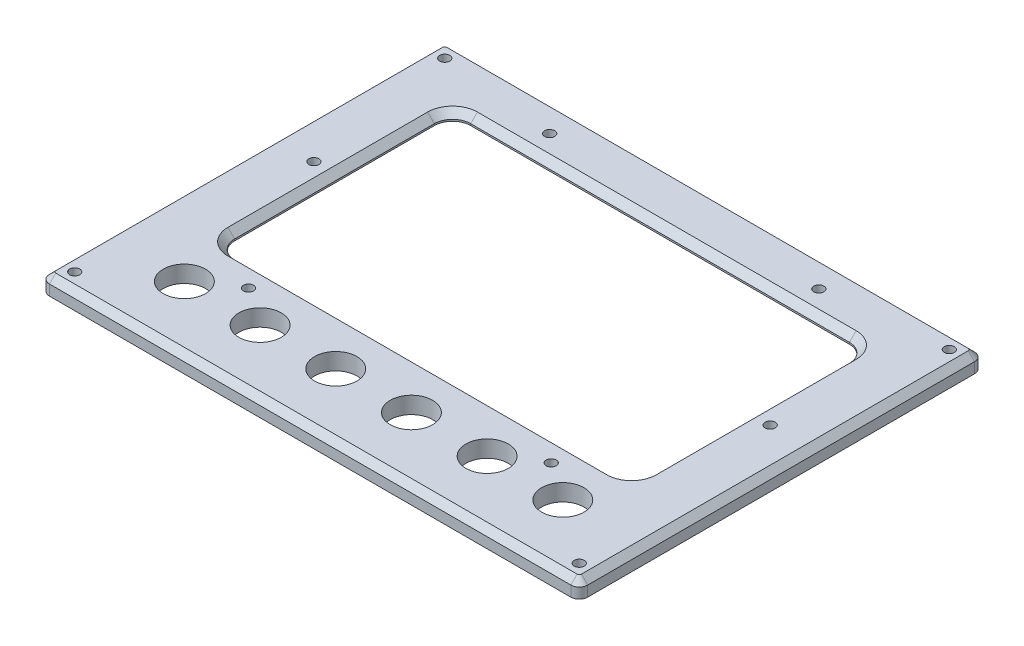
SolidWorks part; units mm, degrees
material "6061-T6 (SS)"
ref_plane "Front Plane" through (0, 0, 0) normal (0, 0, 1) x (1, 0, 0)
ref_plane "Top Plane" through (0, 0, 0) normal (0, 1, 0) x (1, 0, 0)
ref_plane "Right Plane" through (0, 0, 0) normal (1, 0, 0) x (0, 0, -1)
sketch "Sketch1" plane through (0, 0, 0) normal (0, 1, 0) x (1, 0, 0)
  line L1 (-101.6, 64.8558) -> (101.6, 64.8558)
  line L2 (-101.6, 64.8558) -> (-101.6, -87.5442)
  line L3 (-101.6, -87.5442) -> (101.6, -87.5442)
  line L4 (101.6, 64.8558) -> (101.6, -87.5442)
  line L5 (-101.6, 64.8558) -> (101.6, -87.5442) construction
  line L6 (-101.6, -87.5442) -> (101.6, 64.8558) construction
  point P0 (0, -11.3442)
  dimension "D1" = 203.2
  dimension "D2" = 152.4
extrude "Boss-Extrude1" add sketch "Sketch1" along normal blind 6.35
sketch "Sketch2" plane through (0, 6.35, 0) normal (0, 1, 0) x (1, 0, 0)
  line L1 (-78.35, 44.55) -> (78.35, 44.55)
  line L2 (-78.35, 44.55) -> (-78.35, -44.55)
  line L3 (-78.35, -44.55) -> (78.35, -44.55)
  line L4 (78.35, 44.55) -> (78.35, -44.55)
  line L5 (-78.35, 44.55) -> (78.35, -44.55) construction
  line L6 (-78.35, -44.55) -> (78.35, 44.55) construction
  point P0 (0, 0)
  dimension "D1" = 156.7
  dimension "D2" = 89.1
extrude "Cut-Extrude1" cut sketch "Sketch2" against normal through all
fillet "Fillet2" radius 6.858 4 edges at (-78.35, 3.175, 44.55) (78.35, 3.175, 44.55) (78.35, 3.175, -44.55) (-78.35, 3.175, -44.55)
chamfer "Chamfer1" distance 2.54 angle 45 8 edges at (78.35, 6.35, 0) (0, 6.35, 44.55) (-78.35, 6.35, 0) (0, 6.35, -44.55) (76.3413, 6.35, 42.5413) (-76.3413, 6.35, 42.5413) (76.3413, 6.35, -42.5413) (-76.3413, 6.35, -42.5413)
sketch "Sketch7" plane through (0, 0, 0) normal (0, -1, 0) x (1, 0, 0)
  line L1 (-31.75, 54.075) -> (31.75, 54.075)
  line L2 (-31.75, 54.075) -> (-31.75, 44.55)
  line L3 (-31.75, 44.55) -> (31.75, 44.55)
  line L4 (31.75, 54.075) -> (31.75, 44.55)
  line L5 (-31.75, 54.075) -> (31.75, 44.55) construction
  line L6 (-31.75, 44.55) -> (31.75, 54.075) construction
  line L7 (-71.492, 44.55) -> (71.492, 44.55) construction
  point P0 (0, 49.3125)
  dimension "D1" = 63.5
  dimension "D2" = 9.525
extrude "Cut-Extrude4" cut sketch "Sketch7" against normal blind 3.175
fillet "Fillet1" radius 6.858 2 edges at (31.75, 1.5875, 54.075) (-31.75, 1.5875, 54.075)
sketch "Sketch4" plane through (0, 6.35, 0) normal (0, 1, 0) x (1, 0, 0)
  line L0 (-71.4375, -63.6) -> (-42.8625, -63.6) construction
  line L1 (-42.8625, -63.6) -> (-14.2875, -63.6) construction
  line L2 (-14.2875, -63.6) -> (14.2875, -63.6) construction
  line L3 (14.2875, -63.6) -> (42.8625, -63.6) construction
  line L5 (42.8625, -63.6) -> (71.4375, -63.6) construction
  line L6 (-14.2875, -63.6) -> (0, 0) construction
  line L7 (0, 0) -> (14.2875, -63.6) construction
  line L9 (-78.35, -44.55) -> (-31.2102, -44.55) construction
  circle A0 centre (-71.4375, -63.6) radius 8.001
  circle A1 centre (-42.8625, -63.6) radius 8.001
  circle A2 centre (-14.2875, -63.6) radius 8.001
  circle A3 centre (14.2875, -63.6) radius 8.001
  circle A4 centre (42.8625, -63.6) radius 8.001
  circle A5 centre (71.4375, -63.6) radius 8.001
  dimension "D1" = 16.002
  dimension "D2" = 28.575
  dimension "D3" = 19.05
extrude "Cut-Extrude3" cut sketch "Sketch4" against normal through all
fillet "Fillet3" radius 3.175 4 edges at (101.6, 3.175, 87.5442) (101.6, 3.175, -64.8558) (-101.6, 3.175, 87.5442) (-101.6, 3.175, -64.8558)
chamfer "Chamfer2" distance 2.3813 angle 45 8 edges at (101.6, 6.35, 11.3442) (0, 6.35, 87.5442) (0, 6.35, -64.8558) (-101.6, 6.35, 11.3442) (100.6701, 6.35, -63.9259) (100.6701, 6.35, 86.6143) (-100.6701, 6.35, -63.9259) (-100.6701, 6.35, 86.6143)
hole_wizard "#6 Clearance Hole1" positions "Sketch5" profile "Sketch6" hole size "#6" standard "ANSI Inch" end condition through all
sketch "Sketch5" plane through (0, 6.35, 0) normal (0, 1, 0) x (1, 0, 0)
  line L0 (-95.25, 58.5058) -> (0, 0) construction
  line L1 (0, 0) -> (95.25, 58.5058) construction
  line L3 (-98.425, 64.8558) -> (98.425, 64.8558) construction
  line L4 (98.425, -87.5442) -> (-98.425, -87.5442) construction
  line L5 (-101.6, -84.3692) -> (-101.6, 61.6808) construction
  point P0 (-95.25, 58.5058)
  point P2 (95.25, 58.5058)
  point P4 (95.25, -81.1942)
  point P6 (-95.25, -81.1942)
  dimension "D1" = 6.35
  dimension "D2" = 6.35
  dimension "D3" = 6.35
sketch "Sketch6" plane through (-95.25, 6.35, -58.5058) normal (1, 0, 0) x (0, 0, 1)
  line L0 (0, 0) -> (0, 6.35)
  line L1 (0, 6.35) -> (1.8986, 6.35)
  line L2 (1.8986, 6.35) -> (1.8986, 0)
  line L5 (1.8986, 0) -> (0, 0)
  line L11 (0, -6.35) -> (0, 107.95) construction
  dimension "Thru Hole Dia." = 3.7973
  dimension "Thru Hole Depth" = 6.35
sketch "Sketch8" plane through (0, 0, 0) normal (0, -1, 0) x (1, 0, 0)
  line L8 (-88.9, -52.1558) -> (88.9, -52.1558)
  line L9 (88.9, -52.1558) -> (88.9, 74.8442)
  line L10 (88.9, 74.8442) -> (-88.9, 74.8442)
  line L11 (-88.9, 74.8442) -> (-88.9, -52.1558)
  line L12 (-88.9, -52.1558) -> (88.9, -52.1558) construction
  line L13 (88.9, -52.1558) -> (88.9, 74.8442) construction
  line L14 (88.9, 74.8442) -> (-88.9, 74.8442) construction
  line L15 (-88.9, 74.8442) -> (-88.9, -52.1558) construction
  dimension "D1" = 12.7
extrude "Cut-Extrude5" cut sketch "Sketch9" against normal blind 3.175
sketch "Sketch9" plane through (0, 0, 0) normal (0, -1, 0) x (1, 0, 0)
  line L4 (82.45, -50) -> (-82.45, -50) construction
  line L5 (-82.45, -50) -> (-82.45, 50) construction
  line L6 (-82.45, 50) -> (82.45, 50) construction
  line L7 (82.45, 50) -> (82.45, -50) construction
  line L8 (-82.958, 50.508) -> (82.958, 50.508)
  line L9 (82.958, 50.508) -> (82.958, -50.508)
  line L10 (82.958, -50.508) -> (-82.958, -50.508)
  line L11 (-82.958, -50.508) -> (-82.958, 50.508)
sketch "Sketch10" plane through (0, 0, 0) normal (0, -1, 0) x (1, 0, 0)
  line L0 (-82.958, -50.508) -> (-82.958, -43.7728) construction
  line L1 (-82.958, -50.508) -> (-76.2228, -50.508) construction
  line L2 (-82.958, -50.508) -> (82.958, -50.508) construction
  line L3 (-82.958, 50.508) -> (-82.958, -50.508) construction
  circle A0 centre (-79.5904, -47.1404) radius 4.7625
  circle A1 centre (-79.5904, 47.1404) radius 4.7625
  circle A2 centre (79.5904, 47.1404) radius 4.7625
  circle A3 centre (79.5904, -47.1404) radius 4.7625
  dimension "D1" = 9.525
extrude "Cut-Extrude6" cut sketch "Sketch10" against normal up to surface (3.175 mm away) up to face at (0, 3.175, 0)
hole_wizard "#6 Clearance Hole2" positions "Sketch11" profile "Sketch12" hole size "#6" standard "ANSI Inch" end condition through all
sketch "Sketch11" plane through (0, 0, 0) normal (0, -1, 0) x (-1, 0, 0)
  line L0 (-86.133, 0) -> (0, 0)
  line L1 (0, 0) -> (86.133, 0)
  line L3 (-50.8, 53.683) -> (0, 0)
  line L4 (0, 0) -> (50.8, 53.683)
  line L7 (-57.15, -53.683) -> (0, 0)
  line L9 (57.15, -53.683) -> (0, 0)
  line L11 (-82.958, 43.7728) -> (-82.958, -43.7728) construction
  line L12 (-76.2228, -50.508) -> (-30.9088, -50.508) construction
  line L13 (76.2228, 50.508) -> (-76.2228, 50.508) construction
  line L14 (-71.4375, -63.6) -> (-57.15, -53.683)
  line L16 (-42.8625, -63.6) -> (-57.15, -53.683)
  line L19 (-79.5904, 47.1404) -> (-86.133, 0)
  line L22 (-79.5904, -47.1404) -> (-86.133, 0)
  point P0 (-57.15, -53.683)
  point P2 (57.15, -53.683)
  point P4 (86.133, 0)
  point P6 (-86.133, 0)
  point P8 (-50.8, 53.683)
  point P10 (50.8, 53.683)
  dimension "D1" = 3.175
  dimension "D2" = 3.175
  dimension "D3" = 3.175
  dimension "D4" = 101.6
sketch "Sketch12" plane through (57.15, 0, 53.683) normal (1, 0, 0) x (0, 0, -1)
  line L0 (0, 0) -> (0, 6.35)
  line L1 (0, 6.35) -> (1.8986, 6.35)
  line L2 (1.8986, 6.35) -> (1.8986, 0)
  line L5 (1.8986, 0) -> (0, 0)
  line L11 (0, -6.35) -> (0, 107.95) construction
  dimension "Thru Hole Dia." = 3.7973
  dimension "Thru Hole Depth" = 6.35
